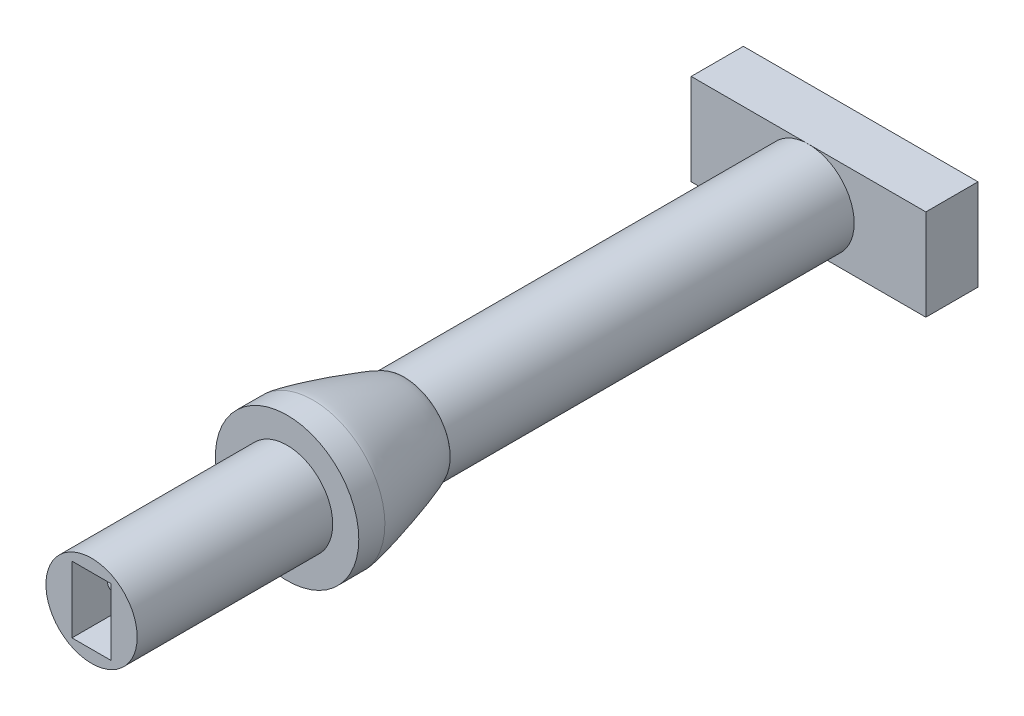
SolidWorks part; units mm, degrees
ref_plane "Piano frontale" through (0, 0, 0) normal (0, 0, 1) x (1, 0, 0)
ref_plane "Piano superiore" through (0, 0, 0) normal (0, 1, 0) x (1, 0, 0)
ref_plane "Piano destro" through (0, 0, 0) normal (1, 0, 0) x (0, 0, -1)
sketch "Schizzo2" plane through (0, 0, 0) normal (0, 0, 1) x (1, 0, 0)
  line L1 (-9, 3.5) -> (9, 3.5)
  line L2 (-9, 3.5) -> (-9, -3.5)
  line L3 (-9, -3.5) -> (9, -3.5)
  line L4 (9, 3.5) -> (9, -3.5)
  line L5 (-9, 3.5) -> (9, -3.5) construction
  line L6 (-9, -3.5) -> (9, 3.5) construction
  point P0 (0, 0)
  dimension "D1" = 18
  dimension "D2" = 7
extrude "Estrusione-Estrusione1" add sketch "Schizzo2" along normal blind 4
sketch "Schizzo3" plane through (0, 0, 4) normal (0, 0, 1) x (1, 0, 0)
  line L0 (0, 3.5) -> (0, -3.5) construction
  line L1 (9, 3.5) -> (-9, 3.5) construction
  line L2 (-9, -3.5) -> (9, -3.5) construction
  circle A0 centre (0, 0) radius 3.5
extrude "Estrusione-Estrusione2" add sketch "Schizzo3" along normal blind 55
sketch "Schizzo4" plane through (0, 0, 59) normal (0, 0, 1) x (1, 0, 0)
  line L1 (-1.5, 2.55) -> (1.5, 2.55)
  line L2 (-1.5, 2.55) -> (-1.5, -2.55)
  line L3 (-1.5, -2.55) -> (1.5, -2.55)
  line L4 (1.5, 2.55) -> (1.5, -2.55)
  line L5 (-1.5, 2.55) -> (1.5, -2.55) construction
  line L6 (-1.5, -2.55) -> (1.5, 2.55) construction
  point P0 (0, 0)
  dimension "D1" = 3
  dimension "D2" = 5.1
extrude "Taglio-Estrusione1" cut sketch "Schizzo4" against normal blind 8.2
sketch "Schizzo5" plane through (-1.5, 0, 0) normal (1, 0, 0) x (0, 0, -1)
  line L0 (-59, 0) -> (-50.8, 0) construction
  line L1 (-59, 2.55) -> (-59, -2.55) construction
  line L2 (-50.8, 2.55) -> (-50.8, -2.55) construction
  circle A0 centre (-54.8, 0) radius 1.5
  dimension "D1" = 3
  dimension "D2" = 4
extrude "Taglio-Estrusione2" cut sketch "Schizzo5" against normal up to next
ref_plane "Piano1" through (0, 0, 44) normal (0, 0, 1) x (1, 0, 0)
sketch "Schizzo6" plane through (0, 0, 44) normal (0, 0, 1) x (1, 0, 0)
  circle A0 centre (0, 0) radius 5.5
  arc A1 (0, -3.5) -> (0, 3.5) centre (0, 0) ccw construction
  dimension "D1" = 2
extrude "Estrusione-Estrusione3" add sketch "Schizzo6" against normal blind 9
fillet "Raccordo1" radius 2 1 edges at (5.5, 0, 35) second distance 7 conic rho 0.1 first distance on face at (3.5, 0, 35)
sketch "Schizzo7" plane through (0, 0, 0) normal (0, 0, -1) x (-1, 0, 0)
  circle A0 centre (0, 0) radius 1
  dimension "D1" = 2
extrude "Taglio-Estrusione3" cut sketch "Schizzo7" against normal blind 2
